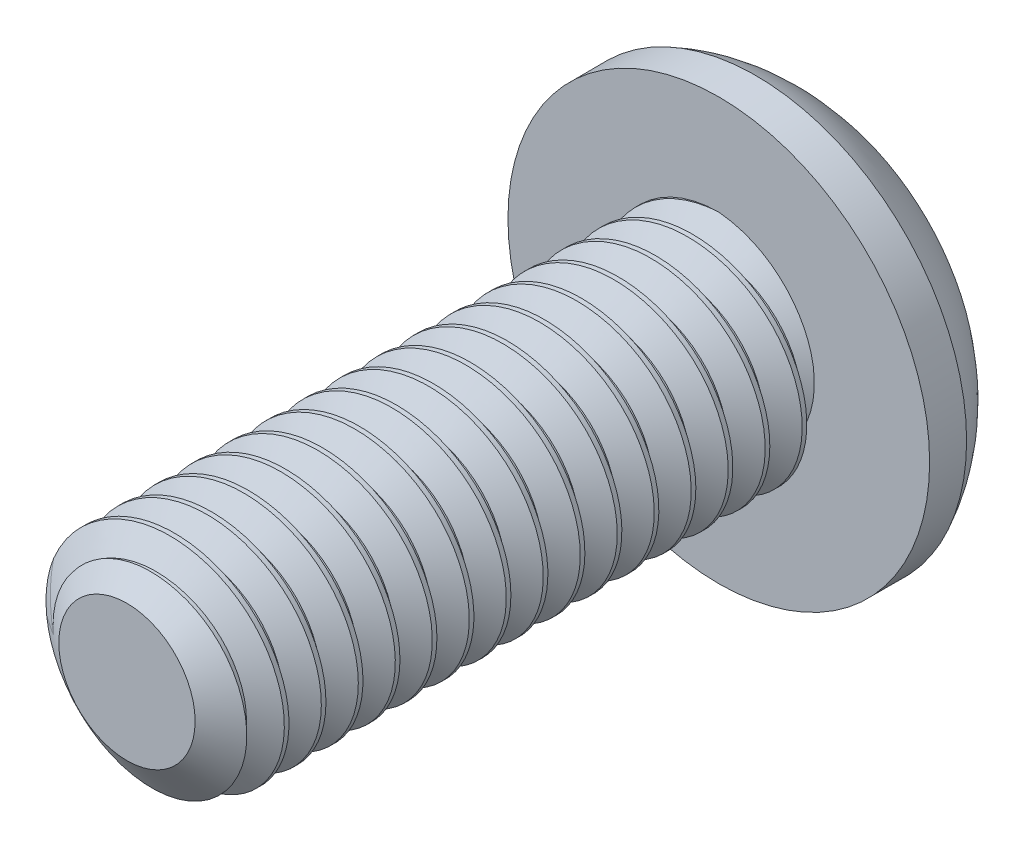
SolidWorks part; units mm, degrees
ref_plane "Front Plane" through (0, 0, 0) normal (0, 0, 1) x (1, 0, 0)
ref_plane "Top Plane" through (0, 0, 0) normal (0, 1, 0) x (1, 0, 0)
ref_plane "Right Plane" through (0, 0, 0) normal (1, 0, 0) x (0, 0, -1)
sketch "Sketch1" plane through (0, 0, 0) normal (0, 0, 1) x (1, 0, 0)
  circle A0 centre (0, 0) radius 1.5
  dimension "OD" = 3
extrude "Extrude1" add sketch "Sketch1" against normal blind 8
sketch "Sketch2" plane through (0, 0, 0) normal (0, 0, 1) x (1, 0, 0)
  circle A0 centre (0, 0) radius 1.5 construction
  circle A1 centre (0, 0) radius 1.5
curve "Helix/Spiral1" pitch 0.5 height 8.5 radius 1.5 centre (0, 0, 0) axis (0, 0, -1) start towards (0, 1, 0) parameters "pitch"=0.5
sketch "Sketch3" plane through (0, 0, 0) normal (1, 0, 0) x (0, 0, -1)
  line L0 (-0.4375, 1.5) -> (-0.25, 1.1752)
  line L1 (-0.25, 1.1752) -> (-0.1875, 1.1752)
  line L2 (-0.1875, 1.1752) -> (0, 1.5)
  line L3 (-0.4375, 1.5) -> (0, 1.5)
  line L4 (-0.2187, 1.5) -> (-0.2187, 1.1752) construction
  line L5 (-0.3437, 1.3376) -> (-0.0937, 1.3376) construction
  line L6 (0, 1.5) -> (0, -1.5) construction
  dimension "D1" = 0.0625
  dimension "D2" = 0.25
  dimension "D3" = 60
sweep "Cut-Sweep1" cut profiles "Sketch3" path "Helix/Spiral1"
sketch "Sketch4" plane through (0, 0, 0) normal (1, 0, 0) x (0, 0, -1)
  line L0 (0.4053, 1.5) -> (0, 0.9212)
  line L1 (0, 0.9212) -> (0, 1.5)
  line L2 (0.4053, 1.5) -> (0, 1.5)
  line L3 (-0.4375, 1.5) -> (0, 1.5) construction
  line L4 (0, 0) -> (7.0209, 0) construction
  dimension "D1" = 55
  dimension "D2" = 0.254
revolve "Cut-Revolve1" cut sketch "Sketch4" angle 360 about L4
sketch "Sketch5" plane through (0, 0, 0) normal (1, 0, 0) x (0, 0, -1)
  line L0 (8, -1.1822) -> (8, 1.0703) construction
  line L1 (8, 1.627) -> (28.1202, 1.627)
  line L2 (8, 1.627) -> (8, 0)
  line L3 (8, 0) -> (28, 0)
  line L4 (28, 1.2968) -> (28, 0)
  line L5 (28.1202, 1.627) -> (28, 1.2968)
  line L6 (0, 0) -> (9.9695, 0) construction
  point P3 (28, 1.627)
  point P10 (28, 1.627)
  dimension "D1" = 0.3302
  dimension "Thread min" = 28
  dimension "D2" = 0.127
  dimension "D3" = 20
revolve "partially thread" [suppressed] add sketch "Sketch5" angle 360 about L6
sketch "Sketch6" plane through (0, 0, -8) normal (0, 0, -1) x (-1, 0, 0)
  circle A0 centre (0, 0) radius 2.85
  dimension "head dia" = 5.7
extrude "Extrude2" add sketch "Sketch6" along normal blind 1.65
sketch "Sketch10" plane through (0, 0, 0) normal (1, 0, 0) x (0, 0, -1)
  line L0 (9.65, -2.85) -> (9.65, 2.85) construction
  line L1 (0, 0) -> (15.9584, 0) construction
  line L2 (9.65, 2.85) -> (8, 2.85) construction
  line L3 (8, 2.85) -> (8, -2.85) construction
  line L4 (8.5, 2.85) -> (8.5, 3.35)
  line L5 (8.5, 3.35) -> (10.15, 3.35)
  line L6 (10.15, 3.35) -> (10.15, 1)
  line L7 (9.65, 1) -> (10.15, 1)
  arc A0 (9.65, 1) -> (8.5, 2.85) centre (7.587, 1) ccw
  dimension "D1" = 2
  dimension "D2" = 0.5
  dimension "D3" = 0.5
revolve "Cut-Revolve2" cut sketch "Sketch10" angle 360 about L1
ref_plane "Plane1" through (0, 0, -9.65) normal (0, 0, 1) x (1, 0, 0)
sketch "Sketch7" plane through (0, 0, -9.65) normal (0, 0, -1) x (-1, 0, 0)
  line L1 (0, 1.1547) -> (-1, 0.5774)
  line L2 (-1, 0.5774) -> (-1, -0.5774)
  line L3 (-1, -0.5774) -> (0, -1.1547)
  line L4 (0, -1.1547) -> (1, -0.5774)
  line L5 (1, -0.5774) -> (1, 0.5774)
  line L6 (1, 0.5774) -> (0, 1.1547)
  circle A0 centre (0, 0) radius 1 construction
  dimension "hex dia" = 2
extrude "Cut-Extrude1" cut sketch "Sketch7" against normal blind 1.5
sketch "Sketch8" plane through (0, 0, -9.65) normal (0, 0, 1) x (1, 0, 0)
  circle A0 centre (0, 0) radius 1.1547
extrude "Cut-Extrude2" cut sketch "Sketch8" along normal through all draft 45
sketch "Sketch9" plane through (0, 0, 0) normal (1, 0, 0) x (0, 0, -1)
  line L0 (0, 1.5) -> (0, -1.5) construction
  line L1 (2.75, 1.5) -> (2.75, -1.5) construction
  dimension "D1" = 2.75
  dimension "D4" = 0.635
  dimension "D5" = 0.3302
equation "\"D3@Helix/Spiral1\" = \"screw length@Extrude1\"+\"pitch@Helix/Spiral1\""
equation "\"D1@Sketch3\" = \"pitch@Helix/Spiral1\"*.125"
equation "\"D2@Sketch3\" = \"pitch@Helix/Spiral1\"*.5"
equation "\"D1@Cut-Extrude1\" = \"hex dia@Sketch7\"*.75"
equation "\"D1@Sketch9\" = \"pitch@Helix/Spiral1\"*5.5"
equation "\"D1@Sketch10\" = \"hex dia@Sketch7\""
equation "\"D1@Plane1\" = \"head depth@Extrude2\""
